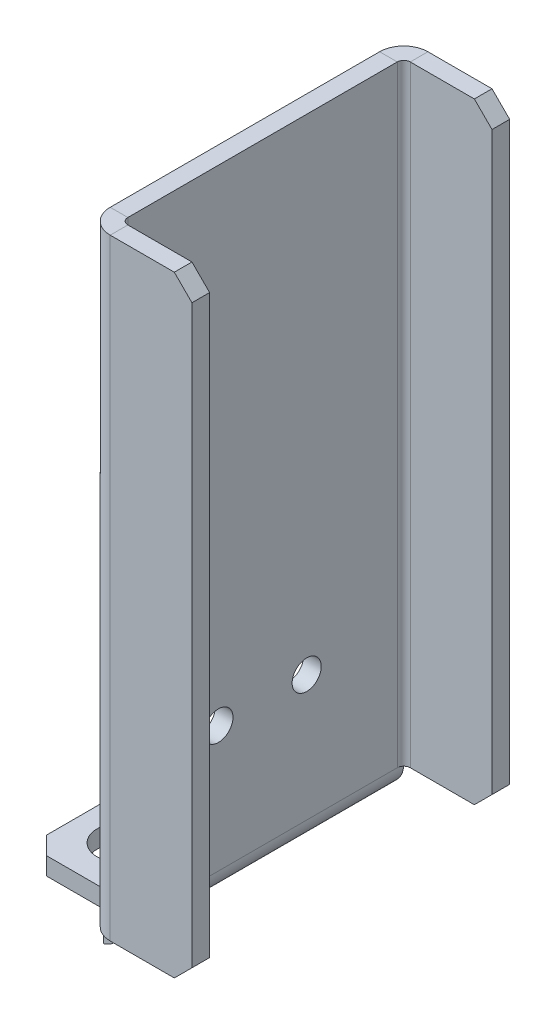
SolidWorks part; units mm, degrees
note: The reader was unsure of these and kept them because the rebuilt part matched: bend radius of "基体折弯1"; flange length of "边线-法兰1".
ref_plane "前视基准面" through (0, 0, 0) normal (0, 0, 1) x (1, 0, 0)
ref_plane "上视基准面" through (0, 0, 0) normal (0, 1, 0) x (1, 0, 0)
ref_plane "右视基准面" through (0, 0, 0) normal (1, 0, 0) x (0, 0, -1)
sketch "草图1" plane through (0, 0, 0) normal (0, 0, 1) x (1, 0, 0)
  line L0 (0, 70) -> (0, 0)
  line L1 (0, 0) -> (-12, 0)
  dimension "D1" = 12
  dimension "D2" = 70
sheet metal parameters "钣金1" thickness 2 parameters "D1"=0.7366
base flange "基体-法兰1" sketch "草图1" end condition mid plane depth 32 reverse direction no thickness 2 reverse thickness direction yes bend radius 0.7366
bend "基体折弯1" bend radius 0.7366 bend angle 90 parameters "D5"=1
sketch "草图3" plane through (0, 0, 0) normal (0, 1, 0) x (1, 0, 0)
  line L0 (0, 0) -> (-41.7757, 0) construction
  line L1 (-12, -16) -> (-12, 16) construction
  circle A0 centre (-7, 7) radius 2.75
  circle A1 centre (-7, -7) radius 2.75
  dimension "D3" = 5.5
  dimension "D1" = 14
  dimension "D2" = 5
extrude "切除-拉伸1" cut sketch "草图3" against normal through all
sketch "草图4" plane through (0, 70, 0) normal (0, 1, 0) x (1, 0, 0)
  line L0 (0, -16) -> (0, 16) construction
  line L1 (-12, 16) -> (0, 16)
  line L2 (-12, 16) -> (-12, 12.5)
  line L3 (-12, 12.5) -> (0, 12.5)
  line L4 (0, 16) -> (0, 12.5)
  line L5 (0, 0) -> (-16.9369, 0) construction
  line L6 (0, -16) -> (0, 16) construction
  line L7 (0, -16) -> (0, -12.5)
  line L8 (-12, -12.5) -> (0, -12.5)
  line L9 (-12, -16) -> (-12, -12.5)
  line L10 (-12, -16) -> (0, -16)
  dimension "D1" = 25
extrude "切除-拉伸2" cut sketch "草图4" against normal through all
edge flange "边线-法兰1" sketch "草图9" flange profiles "草图9", "草图10" flange angle 90 flange length 10 flange position material outside bend radius 0.7366 thickness 2 relief none parameters "D6"=10, "D8"=1
sketch "草图9" plane through (2, 0, 16) normal (0, 0, -1) x (0, 1, 0)
  line L2 (0.7366, 0) -> (0.7366, 10)
  line L3 (0.7366, 10) -> (70, 10)
  line L4 (70, 10) -> (70, 0)
  line L6 (70, 0) -> (0.7366, 0) construction
  line L7 (70, 0) -> (0.7366, 0)
sketch "草图10" plane through (2, 0, -16) normal (0, 0, 1) x (0, -1, 0)
  line L1 (-0.7366, 0) -> (-70, 0) construction
  line L2 (-70, 0) -> (-70, 10)
  line L3 (-70, 10) -> (-0.7366, 10)
  line L4 (-0.7366, 10) -> (-0.7366, 0)
  line L5 (-0.7366, 0) -> (-70, 0)
bend "边线折弯1" bend radius 0.7366 bend angle 90 parameters "D5"=2
bend "边线折弯2" bend radius 0.7366 bend angle 90 parameters "D5"=3
hole_wizard "M4x0.7 螺纹孔1" positions "草图12" profile "草图11" tap size "M4x0.7" standard "JIS"
sketch "草图12" plane through (2, 0, 0) normal (1, 0, 0) x (0, 0, -1)
  line L0 (0, 0) -> (0, 44.2539) construction
  point P1 (-5, 15)
  point P3 (5, 15)
  dimension "D1" = 10
  dimension "D2" = 15
sketch "草图11" plane through (2, 15, 5) normal (0, 1, 0) x (0, 0, -1)
  line L0 (0, 0) -> (0, 11.0914)
  line L1 (0, 11.0914) -> (1.65, 10.1)
  line L2 (1.65, 10.1) -> (1.65, 0)
  line L5 (1.65, 0) -> (0, 0)
  line L10 (0, 11.0914) -> (-1.65, 10.1) construction
  line L11 (0, -6.35) -> (0, 107.95) construction
  dimension "螺纹孔钻头直径" = 3.3
  dimension "螺纹孔钻头深度" = 10.1
  dimension "导头角度" = 118
cosmetic thread "孔螺蚊线1" parameters "D1"=2, "D2"=4
cosmetic thread "孔螺蚊线2" parameters "D1"=2, "D2"=4
chamfer "倒角1" distance 2 angle 45 6 edges at (-12, -1, -12.5) (-12, -1, 12.5) (12, 0.7366, 17) (12, 0.7366, -17) (12, 70, -17) (12, 70, 17)
flat pattern "平板型式1" [suppressed]
sketch "折弯-线1" plane through (2, 0, 0) normal (1, 0, 0) x (0, 0, -1)
  line L0 (-15, 1.3727) -> (15, 1.3727) construction
  line L1 (-15, 1.3727) -> (15, 1.3727) construction
bend of the flat pattern "展开-<基体折弯1>1"
bend of the flat pattern "展开-<边线折弯1>1"
bend of the flat pattern "展开-<边线折弯2>1"
